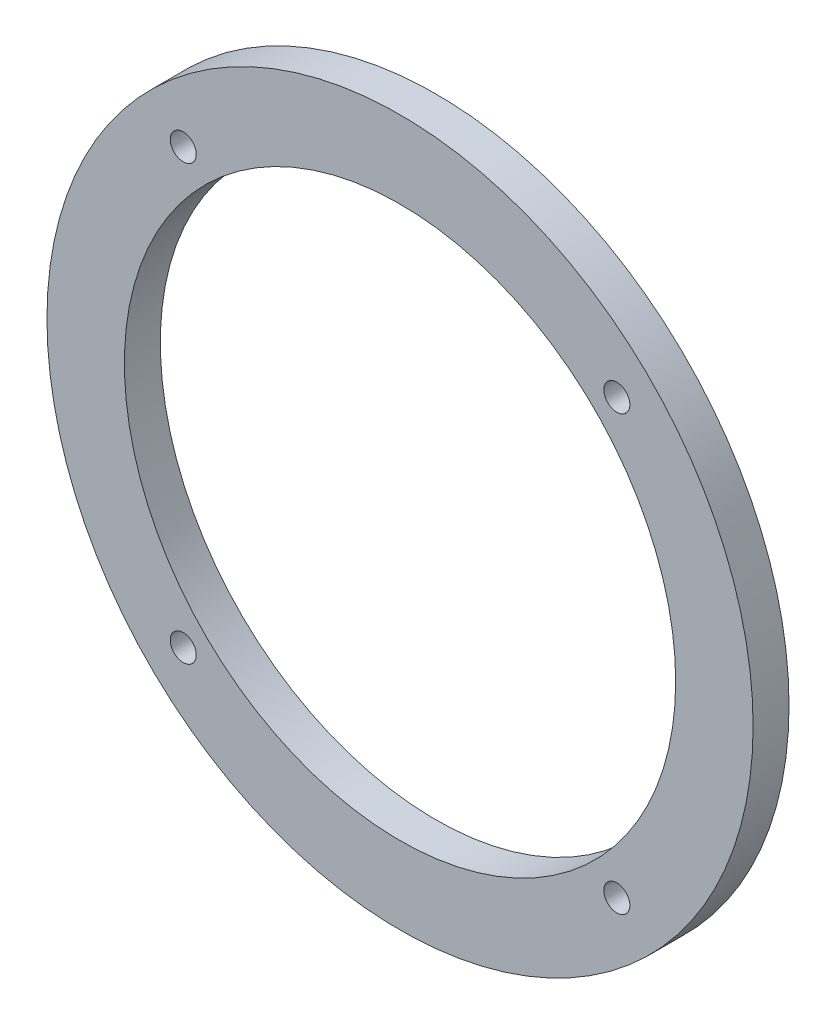
SolidWorks part; units mm, degrees
material "MC901"
ref_plane "正面" through (0, 0, 0) normal (0, 0, 1) x (1, 0, 0)
ref_plane "平面" through (0, 0, 0) normal (0, 1, 0) x (1, 0, 0)
ref_plane "右側面" through (0, 0, 0) normal (1, 0, 0) x (0, 0, -1)
sketch "ｽｹｯﾁ1" plane through (0, 0, 0) normal (0, 0, 1) x (1, 0, 0)
  circle A0 centre (0, 0) radius 44.5
  circle A1 centre (0, 0) radius 57
  dimension "D1" = 114
  dimension "D2" = 89
extrude "ﾎﾞｽ - 押し出し1" add sketch "ｽｹｯﾁ1" along normal blind 5.8
sketch "ｽｹｯﾁ2" plane through (0, 0, 5.8) normal (0, 0, 1) x (1, 0, 0)
  line L1 (-35, 35) -> (35, 35) construction
  line L2 (-35, 35) -> (-35, -35) construction
  line L3 (-35, -35) -> (35, -35) construction
  line L4 (35, 35) -> (35, -35) construction
  line L5 (-35, 35) -> (35, -35) construction
  line L6 (-35, -35) -> (35, 35) construction
  circle A0 centre (35, 35) radius 2.1
  circle A1 centre (35, -35) radius 2.1
  circle A2 centre (-35, -35) radius 2.1
  circle A3 centre (-35, 35) radius 2.1
  point P0 (0, 0)
  point P16 (0, 0)
  dimension "D3" = 4.2
  dimension "D1" = 70
  dimension "D2" = 70
  dimension "D4" = 4
extrude "ｶｯﾄ - 押し出し1" cut sketch "ｽｹｯﾁ2" against normal through all
